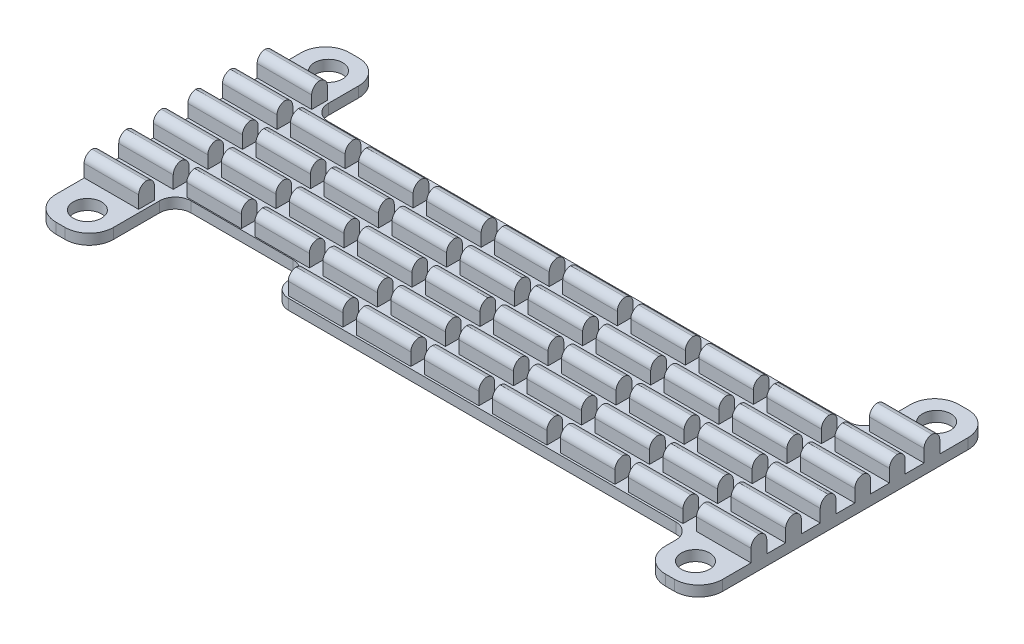
SolidWorks part; units mm, degrees
ref_plane "Płaszczyzna przednia" through (0, 0, 0) normal (0, 0, 1) x (1, 0, 0)
ref_plane "Płaszczyzna górna" through (0, 0, 0) normal (0, 1, 0) x (1, 0, 0)
ref_plane "Płaszczyzna prawa" through (0, 0, 0) normal (1, 0, 0) x (0, 0, -1)
sketch "Szkic1" plane through (0, 0, 0) normal (0, 1, 0) x (1, 0, 0)
  line L0 (0, -11.5) -> (0, 11.5) construction
  line L1 (-31.8, -14) -> (31.8, -14)
  line L2 (-31.8, -14) -> (-31.8, 14)
  line L3 (-31.8, 14) -> (31.8, 14)
  line L4 (31.8, -14) -> (31.8, 14)
  line L5 (-31.8, -14) -> (31.8, 14) construction
  line L6 (-31.8, 14) -> (31.8, -14) construction
  line L7 (-29, 11.5) -> (29, 11.5) construction
  line L8 (-19.3272, 0) -> (19.3272, 0) construction
  circle A0 centre (-29, 11.5) radius 1.35
  circle A1 centre (29, 11.5) radius 1.35
  circle A2 centre (29, -11.5) radius 1.35
  circle A3 centre (-29, -11.5) radius 1.35
  point P0 (0, 0)
  point P9 (0, 0)
  point P12 (0, 11.5)
  point P15 (0, 0)
  dimension "D5" = 2.7
  dimension "D6" = 2.7
  dimension "D1" = 63.6
  dimension "D2" = 28
  dimension "D3" = 23
  dimension "D4" = 58
extrude "Dodanie-wyciągnięcie1" add sketch "Szkic1" along normal blind 1
sketch "Szkic4" plane through (31.8, 0, 0) normal (1, 0, 0) x (0, 0, -1)
  line L0 (14, 1) -> (9, 1) construction
  line L1 (-14, 1) -> (14, 1) construction
  line L2 (9, 1) -> (9, 3)
  line L3 (9, 3) -> (7.5, 3)
  line L4 (7.5, 3) -> (7.5, 1)
  line L5 (7.5, 1) -> (9, 1)
  dimension "D1" = 5
  dimension "D2" = 1.5
  dimension "D3" = 2
extrude "Dodanie-wyciągnięcie2" add sketch "Szkic4" against normal blind 5.2 contours L2 L3 L4 L5
fillet "Zaokrąglenie3" radius 0.8 2 edges at (29.2, 3, -7.5) (29.2, 3, -9)
pattern_linear "Szyk liniowy1" count 6 spacing 3.3 along (0, 0, 1) count 10 spacing 6.49 along (-1, 0, 0) of "Zaokrąglenie3", "Dodanie-wyciągnięcie2"
sketch "Szkic2" plane through (0, 0, 0) normal (0, 1, 0) x (1, 0, 0)
  line L0 (-31.8, 14) -> (-26.32, 14) construction
  line L1 (31.8, 14) -> (-31.8, 14) construction
  line L2 (-26.32, 14) -> (-26.32, 7.3)
  line L3 (-26.32, 7.3) -> (26.32, 7.3)
  line L4 (26.32, 7.3) -> (26.32, 14)
  line L5 (26.32, 14) -> (31.8, 14) construction
  line L6 (-26.32, 14) -> (26.32, 14)
  line L7 (-31.8, -14) -> (-26.32, -14) construction
  line L8 (-31.8, -14) -> (31.8, -14) construction
  line L9 (-13.6, -5.8) -> (-26.32, -5.8)
  line L10 (-26.32, -5.8) -> (-26.32, -14)
  line L11 (-26.32, -14) -> (26.32, -14)
  line L13 (-13.6, -5.8) -> (-13.6, -9.2)
  line L14 (-13.6, -9.2) -> (26.32, -9.2)
  line L15 (26.32, -9.2) -> (26.32, -14)
  line L16 (26.32, -14) -> (31.8, -14) construction
  point P15 (-31.8, -14)
  point P18 (0, 0)
  dimension "D1" = 4.8
  dimension "D2" = 3.4
  dimension "D3" = 6.7
  dimension "D4" = 12.72
  dimension "D5" = 5.48
  dimension "D6" = 5.48
  dimension "D7" = 5.48
  dimension "D8" = 5.48
extrude "Wytnij-wyciągnięcie1" cut sketch "Szkic2" along normal through all
fillet "Zaokrąglenie1" radius 2.3 8 edges at (-31.8, 0.5, 14) (-31.8, 0.5, -14) (31.8, 0.5, -14) (31.8, 0.5, 14) (-26.32, 0.5, -14) (26.32, 0.5, -14) (26.32, 0.5, 14) (-26.32, 0.5, 14)
fillet "Zaokrąglenie2" radius 1.5 6 edges at (-26.32, 0.5, -7.3) (26.32, 0.5, -7.3) (26.32, 0.5, 9.2) (-13.6, 0.5, 5.8) (-13.6, 0.5, 9.2) (-26.32, 0.5, 5.8)
